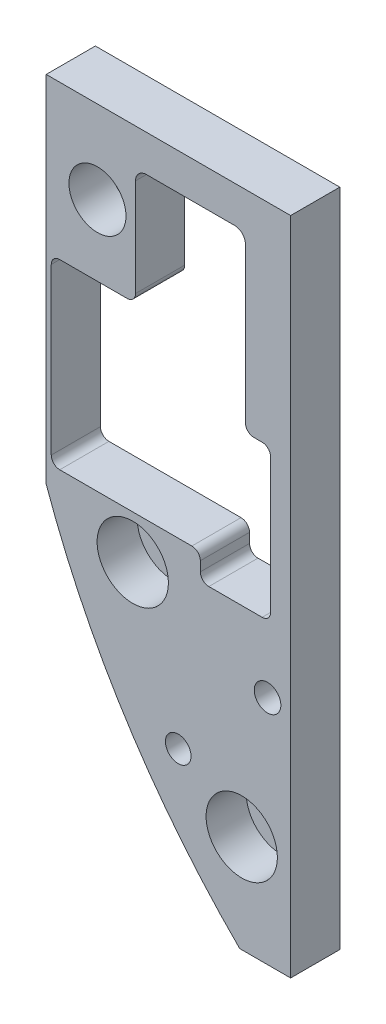
SolidWorks part; units mm, degrees
material "PET"
ref_plane "Front" through (0, 0, 0) normal (0, 0, 1) x (1, 0, 0)
ref_plane "Top" through (0, 0, 0) normal (0, 1, 0) x (1, 0, 0)
ref_plane "Right" through (0, 0, 0) normal (1, 0, 0) x (0, 0, -1)
sketch "Sketch1" plane through (0, 0, 0) normal (0, 0, 1) x (1, 0, 0)
  line L4 (0, -17.78) -> (-45.72, -17.78)
  line L5 (-45.72, -17.78) -> (-45.72, -84.1375)
  line L6 (-9.525, -141.2875) -> (0, -141.2875)
  line L7 (0, -141.2875) -> (0, -17.78)
  line L8 (0, -17.78) -> (-45.72, -17.78)
  line L9 (-45.72, -17.78) -> (-45.72, -84.1375)
  line L10 (-9.525, -141.2875) -> (0, -141.2875)
  line L11 (0, -141.2875) -> (0, -17.78)
  line L17 (-30.5943, -46.5015) -> (-43.1857, -46.5015)
  line L18 (-44.7732, -48.089) -> (-44.7732, -78.9652)
  line L19 (-43.1857, -80.5527) -> (-18.4742, -80.5527)
  line L20 (-16.8867, -82.1402) -> (-16.8867, -83.9371)
  line L21 (-15.2992, -85.5246) -> (-5.3275, -85.5246)
  line L22 (-3.74, -83.9371) -> (-3.74, -58.7502)
  line L23 (-6.8707, -57.1627) -> (-5.3275, -57.1627)
  line L80 (-8.4582, -55.1307) -> (-8.4582, -26.6573)
  line L81 (-26.9748, -57.1627) -> (-10.4902, -57.1627)
  line L82 (-29.0068, -26.6573) -> (-29.0068, -55.1307)
  line L83 (-10.4902, -24.6253) -> (-26.9748, -24.6253)
  line L84 (-8.4582, -55.5752) -> (-8.4582, -26.6573)
  line L86 (-29.0068, -26.6573) -> (-29.0068, -44.914)
  line L87 (-10.4902, -24.6253) -> (-26.9748, -24.6253)
  circle A1 centre (-36.1315, -33.274) radius 2.1526
  circle A2 centre (-36.1315, -33.274) radius 2.1527
  circle A5 centre (-9.144, -122.9995) radius 2.1526
  circle A6 centre (-9.144, -122.9995) radius 2.1527
  arc A7 (-45.72, -84.1375) -> (-9.525, -141.2875) centre (97.9169, -33.2042) ccw
  arc A8 (-45.72, -84.1375) -> (-9.525, -141.2875) centre (97.9169, -33.2042) ccw
  arc A9 (-3.74, -58.7502) -> (-5.3275, -57.1627) centre (-5.3275, -58.7502) ccw
  arc A10 (-8.4582, -55.5752) -> (-6.8707, -57.1627) centre (-6.8707, -55.5752) ccw
  arc A11 (-30.5943, -46.5015) -> (-29.0068, -44.914) centre (-30.5943, -44.914) ccw
  arc A12 (-43.1857, -46.5015) -> (-44.7732, -48.089) centre (-43.1857, -48.089) ccw
  arc A13 (-44.7732, -78.9652) -> (-43.1857, -80.5527) centre (-43.1857, -78.9652) ccw
  arc A14 (-18.4742, -80.5527) -> (-16.8867, -82.1402) centre (-18.4742, -82.1402) cw
  arc A15 (-16.8867, -83.9371) -> (-15.2992, -85.5246) centre (-15.2992, -83.9371) ccw
  arc A16 (-8.4582, -26.6573) -> (-10.4902, -24.6253) centre (-10.4902, -26.6573) ccw
  arc A17 (-10.4902, -57.1627) -> (-8.4582, -55.1307) centre (-10.4902, -55.1307) ccw
  arc A18 (-29.0068, -55.1307) -> (-26.9748, -57.1627) centre (-26.9748, -55.1307) ccw
  arc A19 (-26.9748, -24.6253) -> (-29.0068, -26.6573) centre (-26.9748, -26.6573) ccw
  arc A20 (-8.4582, -26.6573) -> (-10.4902, -24.6253) centre (-10.4902, -26.6573) ccw
  arc A23 (-26.9748, -24.6253) -> (-29.0068, -26.6573) centre (-26.9748, -26.6573) ccw
  arc A24 (-5.3275, -85.5246) -> (-3.74, -83.9371) centre (-5.3275, -83.9371) ccw
  circle A25 centre (-4.3174, -98.0359) radius 2.487
  circle A26 centre (-21.0247, -114.6804) radius 2.3945
  dimension "D5" = 1.5875
  dimension "D1" = 0
  dimension "D3" = 0
  dimension "D4" = 0
  dimension "D9" = 1.27
extrude "Boss-Extrude1" add sketch "Sketch1" along normal blind 10.8
sketch "Sketch3" plane through (0, 0, 10.8) normal (0, 0, 1) x (1, 0, 0)
  circle A0 centre (-9.144, -122.9995) radius 6.6675
  circle A1 centre (-29.5275, -88.7095) radius 6.6675
  circle A3 centre (-36.1315, -33.274) radius 5.334
  dimension "D1" = 10.668
  dimension "D2" = 13.335
  dimension "D3" = 13.335
extrude "Cut-Extrude1" cut sketch "Sketch3" against normal blind 7.5
sketch "Sketch4" plane through (0, 0, 0) normal (0, 0, -1) x (-1, 0, 0)
  line L4 (0, -17.78) -> (0, -141.2875)
  line L5 (0, -141.2875) -> (9.525, -141.2875)
  line L6 (45.72, -84.1375) -> (45.72, -17.78)
  line L7 (45.72, -17.78) -> (0, -17.78)
  line L8 (0, -17.78) -> (0, -141.2875)
  line L9 (0, -141.2875) -> (9.525, -141.2875)
  line L10 (45.72, -84.1375) -> (45.72, -17.78)
  line L11 (45.72, -17.78) -> (0, -17.78)
  arc A1 (9.525, -141.2875) -> (45.72, -84.1375) centre (-97.9169, -33.2042) ccw
  arc A2 (9.525, -141.2875) -> (45.72, -84.1375) centre (-97.9169, -33.2042) ccw
  dimension "D1" = 0
extrude "Cut-Extrude2" cut sketch "Sketch4" against normal blind 1.6
